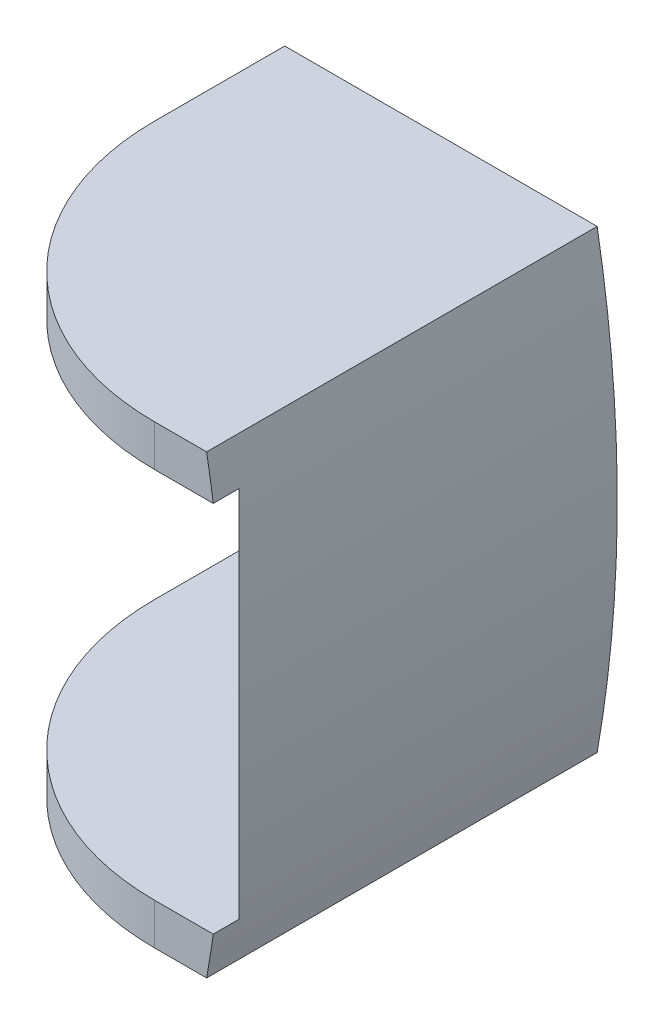
SolidWorks part; units mm, degrees
ref_plane "Front Plane" through (0, 0, 0) normal (0, 0, 1) x (1, 0, 0)
ref_plane "Top Plane" through (0, 0, 0) normal (0, 1, 0) x (1, 0, 0)
ref_plane "Right Plane" through (0, 0, 0) normal (1, 0, 0) x (0, 0, -1)
sketch "Sketch6" plane through (0, 0, 0) normal (0, 1, 0) x (1, 0, 0)
  line L1 (-12, 15) -> (12, 15)
  line L2 (-12, 15) -> (-12, -15)
  line L3 (-12, -15) -> (12, -15)
  line L4 (12, 15) -> (12, -15)
  line L5 (-12, 15) -> (12, -15) construction
  line L6 (-12, -15) -> (12, 15) construction
  point P0 (0, 0)
  dimension "D1" = 24
  dimension "D2" = 30
extrude "Boss-Extrude5" add sketch "Sketch6" along normal blind 35
sketch "Sketch10" plane through (0, 0, -15) normal (0, 0, -1) x (-1, 0, 0)
  line L0 (-12, 0) -> (-12, 35)
  arc A1 (-12, 0) -> (-12, 35) centre (86.4568, 17.5) cw
  dimension "D1" = 100
extrude "Boss-Extrude6" add sketch "Sketch10" against normal up to surface (30 mm away) up to face at (0, 17.5, 15)
ref_plane "Plane1" through (0, 17.5, 0) normal (0, 1, 0) x (1, 0, 0)
sketch "Sketch8" plane through (0, 17.5, 0) normal (0, 1, 0) x (1, 0, 0)
  line L0 (-12, 11.5) -> (-12, -15)
  line L1 (-12, 15) -> (-12, -15) construction
  line L4 (14.5, -15) -> (-12, 11.5)
  line L5 (12, 15) -> (-12, 15) construction
  line L6 (-12, -15) -> (14.5, -15)
  line L7 (-12, -15) -> (12, -15) construction
  dimension "D1" = 3.5
  dimension "D2" = 45
extrude "Cut-Extrude1" cut sketch "Sketch8" against normal offset from surface (14.325 mm away) 3.175 up to face at (0, 0, 0)
mirror "Mirror2" about plane through (0, 17.5, 0) normal (0, 1, 0) of "Cut-Extrude1"
fillet "Fillet1" radius 20 2 edges at (-12, 1.5875, 15) (-12, 33.4125, 15)
sketch "Sketch9" plane through (0, 0, -15) normal (0, 0, -1) x (-1, 0, 0)
  line L0 (12, 17.5) -> (-13.5432, 17.5) construction
  line L3 (12, 35) -> (12, 0) construction
  circle A0 centre (2.4568, 17.5) radius 2.7
  circle A1 centre (-7.5432, 17.5) radius 2.7
  arc A3 (-12, 35) -> (-12, 0) centre (86.4568, 17.5) ccw construction
  dimension "D1" = 5.4
  dimension "D2" = 10
  dimension "D3" = 6
extrude "Cut-Extrude2" cut sketch "Sketch9" against normal blind 8
sketch "Sketch11" plane through (-0.25, 0, 0.25) normal (-0.7071, 0, 0.7071) x (0.7071, 0, 0.7071)
  line L0 (-16.617, 17.5) -> (19.5587, 17.5) construction
  line L1 (-16.617, 3.175) -> (-16.617, 31.825) construction
  circle A0 centre (-1.175, 6.65) radius 1.65
  circle A1 centre (5.175, 6.65) radius 1.65
  circle A2 centre (5.175, 28.35) radius 1.65
  circle A3 centre (-1.175, 28.35) radius 1.65
  dimension "D1" = 3.3
extrude "Cut-Extrude3" cut sketch "Sketch11" against normal blind 9
